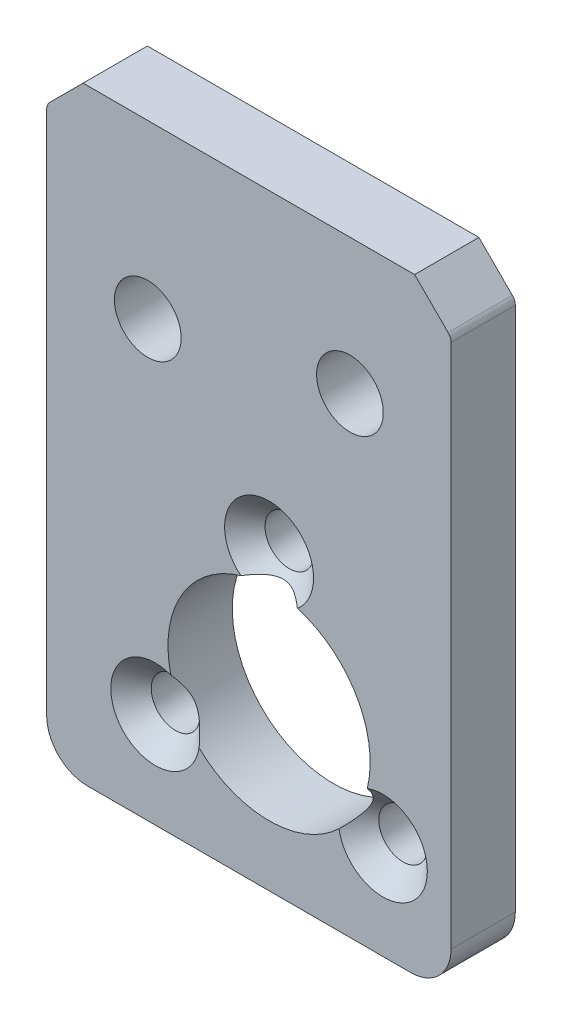
SolidWorks part; units mm, degrees
ref_plane "Front Plane" through (0, 0, 0) normal (0, 0, 1) x (1, 0, 0)
ref_plane "Top Plane" through (0, 0, 0) normal (0, 1, 0) x (1, 0, 0)
ref_plane "Right Plane" through (0, 0, 0) normal (1, 0, 0) x (0, 0, -1)
sketch "Sketch12" plane through (0, 0, 0) normal (0, 0, 1) x (1, 0, 0)
  line L0 (-20, -30) -> (0, -30)
  line L1 (-20, -30) -> (-20, 0)
  line L2 (0, -30) -> (0, 0)
  line L3 (-20, 0) -> (0, 0)
  line L4 (-9, -15.4999) -> (-14.6292, -25.25) construction
  line L5 (-14.6292, -25.25) -> (-3.3708, -25.25) construction
  line L6 (-3.3708, -25.25) -> (-9, -15.4999) construction
  circle A0 centre (-9, -22) radius 6.5001 construction
  circle A6 centre (-9, -22) radius 5
  circle A7 centre (-5, -6.7) radius 1.65
  circle A8 centre (-15, -8.5) radius 1.65
  point P8 (-3.3708, -25.25)
  point P11 (-14.6292, -25.25)
  point P12 (-10.1709, -15.6063)
  point P13 (-9, -15.4999)
  dimension "D1" = 3.3
  dimension "D8" = 10
  dimension "D9" = 13.0001
  dimension "D2" = 30
  dimension "D3" = 6.7
  dimension "D4" = 8.5
  dimension "D5" = 5
  dimension "D6" = 15
  dimension "D7" = 22
  dimension "D10" = 9
  dimension "D11" = 20
extrude "Boss-Extrude3" add sketch "Sketch12" along normal blind 3.18
hole_wizard "CSK for M2 Flat Head Machine Screw2" positions "Sketch13" profile "Sketch15" countersink size "M2" standard "ANSI Metric" end condition through all
sketch "Sketch13" plane through (0, 0, 3.18) normal (0, 0, 1) x (1, 0, 0)
  point P0 (-9, -15.4999)
  point P3 (-14.6292, -25.25)
  point P6 (-3.3708, -25.25)
sketch "Sketch15" plane through (-9, -15.4999, 3.18) normal (1, 0, 0) x (0, -1, 0)
  line L0 (0, 0) -> (0, 3.18)
  line L1 (0, 3.18) -> (1.2, 3.18)
  line L2 (1.2, 3.18) -> (1.2, 1)
  line L3 (1.2, 1) -> (2.2, 0)
  line L5 (2.2, 0) -> (0, 0)
  line L6 (-1.2, 1) -> (-2.2, 0) construction
  line L11 (0, -6.35) -> (0, 107.95) construction
  dimension "Thru Hole Dia." = 2.4
  dimension "Thru Hole Depth" = 3.18
  dimension "Near C'Sink Dia." = 4.4
  dimension "Near C'Sink Angle" = 90
chamfer "Chamfer1" distance 1.8 angle 45 2 edges at (-20, 0, 1.59) (0, 0, 1.59)
fillet "Fillet3" radius 0.5 2 edges at (-20, -1.8, 1.59) (0, -1.8, 1.59)
fillet "Fillet4" radius 2 2 edges at (-20, -30, 1.59) (0, -30, 1.59)
